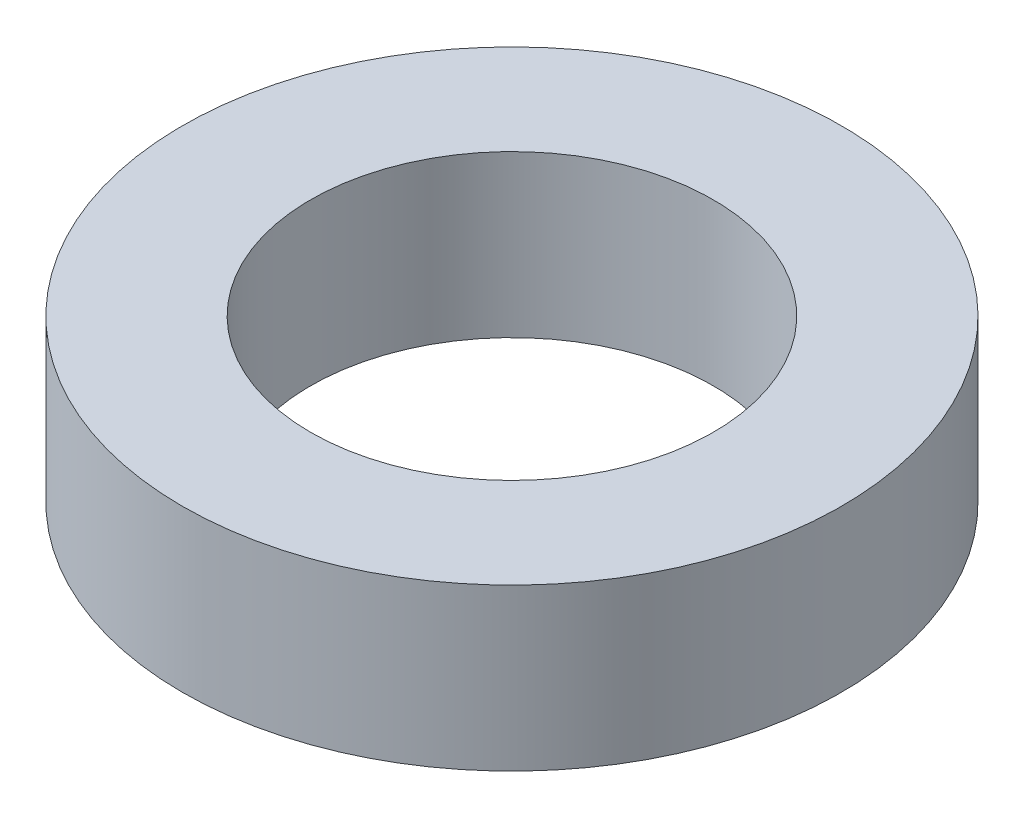
SolidWorks part; units mm, degrees
ref_plane "Front Plane" through (0, 0, 0) normal (0, 0, 1) x (1, 0, 0)
ref_plane "Top Plane" through (0, 0, 0) normal (0, 1, 0) x (1, 0, 0)
ref_plane "Right Plane" through (0, 0, 0) normal (1, 0, 0) x (0, 0, -1)
sketch "Sketch1" plane through (0, 0, 0) normal (0, 1, 0) x (1, 0, 0)
  circle A0 centre (0, 0) radius 45
  dimension "FLANGE_OD" = 90
extrude "Boss-Extrude1" add sketch "Sketch1" along normal blind 22
sketch "Sketch2" plane through (0, 0, 0) normal (0, 1, 0) x (1, 0, 0)
  circle A0 centre (0, 0) radius 27.5
  dimension "BORE_D" = 55
extrude "Cut-Extrude1" cut sketch "Sketch2" along normal through all
sketch "Sketch3" plane through (0, 22, 0) normal (0, 1, 0) x (1, 0, 0)
  circle A0 centre (0, 0) radius 16.4718 construction
  circle A1 centre (-16.4718, 0) radius 2.8697
  dimension "BOLT_D" = 5.7394
  dimension "BOLT_PCD" = 32.9436
extrude "Cut-Extrude2" cut sketch "Sketch3" against normal blind 13.2316 rebuild error yes
pattern_circular "CirPattern1" count 6 over 360 rebuild error yes
